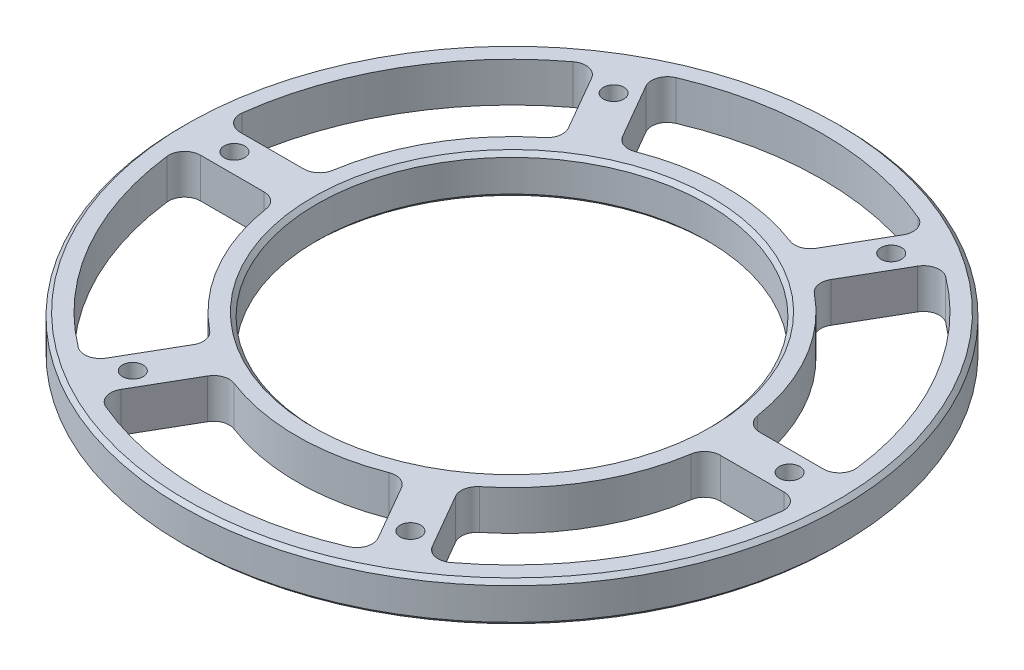
SolidWorks part; units mm, degrees
ref_plane "Front Plane" through (0, 0, 0) normal (0, 0, 1) x (1, 0, 0)
ref_plane "Top Plane" through (0, 0, 0) normal (0, 1, 0) x (1, 0, 0)
ref_plane "Right Plane" through (0, 0, 0) normal (1, 0, 0) x (0, 0, -1)
sketch "Sketch2" plane through (0, 0, 0) normal (1, 0, 0) x (0, 0, -1)
  line L0 (-49.2125, 0) -> (-83.0999, 0)
  line L1 (-83.0999, 0) -> (-83.0999, 10)
  line L2 (-83.0999, 10) -> (-49.2125, 10)
  line L3 (-49.2125, 10) -> (-49.2125, 0)
  dimension "D1" = 83.0999
  dimension "D2" = 10
  dimension "D4" = 49.2125
ref_axis "Axis1" through (0, -0.5, 0) along (0, 1, 0)
revolve "Revolve1" add sketch "Sketch2" angle 360 about axis through (0, -0.5, 0) along (0, 1, 0)
hole_wizard "#6 (0.204) Diameter Hole1" positions "Sketch6" profile "Sketch7" hole size "#6" standard "ANSI Inch" end condition through all
sketch "Sketch6" plane through (0, 10, 0) normal (0, 1, 0) x (1, 0, 0)
  line L0 (0, 0) -> (-69.8201, 120.932) construction
  line L2 (0, 0) -> (0, 109.0908) construction
  point P0 (-35, 60.6218)
  dimension "D1" = 30
  dimension "D2" = 70
sketch "Sketch7" plane through (-35, 10, -60.6218) normal (1, 0, 0) x (0, 0, 1)
  line L0 (0, 0) -> (0, 10)
  line L1 (0, 10) -> (2.5908, 10)
  line L2 (2.5908, 10) -> (2.5908, 0)
  line L5 (2.5908, 0) -> (0, 0)
  line L11 (0, -6.35) -> (0, 107.95) construction
  dimension "Thru Hole Dia." = 5.1816
  dimension "Thru Hole Depth" = 10
pattern_circular "CirPattern3" count 6 over 360 about axis through (0, -0.5, 0) along (0, 1, 0) of "#6 (0.204) Diameter Hole1"
sketch "Sketch8" plane through (0, 10, 0) normal (0, 1, 0) x (1, 0, 0)
  line L4 (0, 0) -> (0, 93.9995) construction
  line L5 (-22.6606, 49.2493) -> (-34.6397, 69.9978)
  line L6 (22.6606, 49.2493) -> (34.6397, 69.9978)
  line L7 (0, 0) -> (-35, 60.6218) construction
  arc A0 (-22.6606, 49.2493) -> (22.6606, 49.2493) centre (0, 0) cw
  arc A1 (-34.6397, 69.9978) -> (34.6397, 69.9978) centre (0, 0) cw
  circle A2 centre (0, 0) radius 83.0999 construction
  circle A4 centre (0, 0) radius 49.2125 construction
  dimension "D1" = 5
  dimension "D2" = 5
  dimension "D3" = 5
extrude "Cut-Extrude1" cut sketch "Sketch8" against normal through all
fillet "Fillet1" radius 4 4 edges at (-22.6606, 5, -49.2493) (22.6606, 5, -49.2493) (34.6397, 5, -69.9978) (-34.6397, 5, -69.9978)
pattern_circular "CirPattern4" count 6 over 360 about axis through (0, -0.5, 0) along (0, 1, 0) of "Cut-Extrude1", "Fillet1"
chamfer "Chamfer1" distance 1 angle 45 2 edges at (0, 10, -49.2125) (0, 0, -49.2125)
chamfer "Chamfer2" distance 1 angle 45 2 edges at (0, 10, -83.0999) (0, 0, -83.0999)
equation "\"TubeDiameter\" = 6.5433in"
equation "\"D1@Sketch2\"=\"TubeDiameter\"/2"
